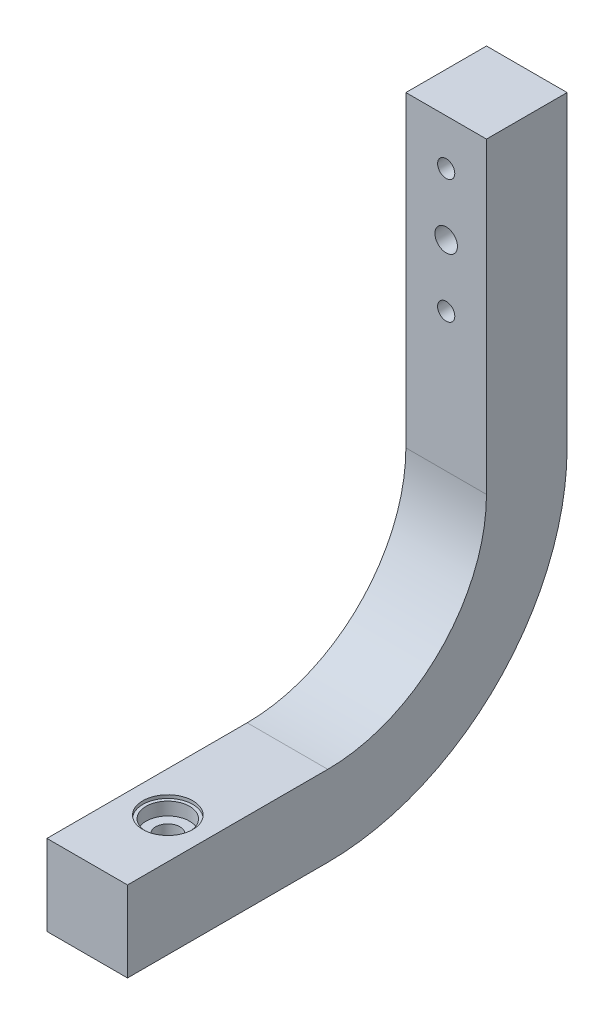
SolidWorks part; units mm, degrees
ref_plane "Front Plane" through (0, 0, 0) normal (0, 0, 1) x (1, 0, 0)
ref_plane "Top Plane" through (0, 0, 0) normal (0, 1, 0) x (1, 0, 0)
ref_plane "Right Plane" through (0, 0, 0) normal (1, 0, 0) x (0, 0, -1)
ref_axis "Z" through (0, 0, 86.1) along (0, 0, -1)
sketch "Sketch1" plane through (0, 0, 0) normal (1, 0, 0) x (0, 0, -1)
  line L0 (-15, 20) -> (0, 20)
  line L1 (0, 20) -> (0, -37.2682)
  line L2 (0, -32) -> (-49.8046, -81.8046) construction
  line L3 (-44.5364, -81.8046) -> (-66.8046, -81.8046)
  line L4 (-66.8046, -81.8046) -> (-66.8046, -66.8046) construction
  line L5 (-66.8046, -66.8046) -> (-44.5364, -66.8046)
  line L6 (-56.0178, -66.8046) -> (-15, -25.7868) construction
  line L7 (-15, -37.2682) -> (-15, 20)
  line L8 (-35.5089, -46.2957) -> (-24.9023, -56.9023) construction
  line L9 (-44.5364, -66.8046) -> (-56.0178, -66.8046) construction
  line L10 (-66.8046, -66.8046) -> (-81.8046, -66.8046)
  line L11 (-66.8046, -66.8046) -> (-66.8046, -81.8046) construction
  line L12 (-66.8046, -81.8046) -> (-81.8046, -81.8046)
  line L13 (-81.8046, -66.8046) -> (-81.8046, -81.8046)
  line L14 (-15, -25.7868) -> (-15, -37.2682) construction
  line L15 (0, -37.2682) -> (0, -32) construction
  line L16 (-49.8046, -81.8046) -> (-44.5364, -81.8046) construction
  arc A0 (-44.5364, -66.8046) -> (-15, -37.2682) centre (-44.5364, -37.2682) ccw
  arc A1 (-44.5364, -81.8046) -> (0, -37.2682) centre (-44.5364, -37.2682) ccw
  dimension "D1" = 15
  dimension "D2" = 66.8046
  dimension "D3" = 81.8046
  dimension "D4" = 20
  dimension "D5" = 135
  dimension "D6" = 49.8046
  dimension "D7" = 15
  dimension "D8" = 22.2682
extrude "Boss-Extrude1" add sketch "Sketch1" along normal blind 7.5 and the other way blind 7.5
sketch "Sketch3" plane through (0, -66.8046, 0) normal (0, 1, 0) x (1, 0, 0)
  line L0 (-8.25, 0) -> (8.25, 0) construction
  line L1 (0, -45.1) -> (0, 45.1) construction
  circle A0 centre (0, -66.8046) radius 2.25
  dimension "D2" = 4.5
  dimension "D1" = 66.8046
extrude "Cut-Extrude1" cut sketch "Sketch3" against normal through all
sketch "Sketch4" plane through (0, 0, 15) normal (0, 0, 1) x (1, 0, 0)
  line L0 (0, -11.5) -> (0, 11.5) construction
  circle A0 centre (0, 0) radius 2.1
  circle A1 centre (0, 11.5) radius 1.6
  circle A2 centre (0, -11.5) radius 1.6
  dimension "D1" = 4.2
  dimension "D3" = 3.2
  dimension "D2" = 23
extrude "Cut-Extrude2" cut sketch "Sketch4" against normal through all both and the other way through all
ref_axis "Axis1" through (0, -52.1687, 66.8046) along (0, 1, 0)
sketch "Sketch5" plane through (0, 0, 0) normal (1, 0, 0) x (0, 0, -1)
  line L0 (-62.7546, -78.8046) -> (-62.7546, -81.2046)
  line L1 (-62.7546, -81.2046) -> (-62.1546, -81.2046)
  line L2 (-62.1546, -81.2046) -> (-62.1546, -81.8046)
  line L3 (-62.1546, -81.8046) -> (-66.8046, -81.8046)
  line L4 (-66.8046, -81.8046) -> (-66.8046, -78.8046)
  line L5 (-66.8046, -78.8046) -> (-62.7546, -78.8046)
  line L6 (-66.8046, -74.3046) -> (-66.8046, -90.6731) construction
  line L7 (-66.8046, -74.3046) -> (-81.8046, -74.3046) construction
  line L8 (-66.8046, -69.8046) -> (-62.7546, -69.8046)
  line L9 (-66.8046, -66.8046) -> (-66.8046, -69.8046)
  line L10 (-62.1546, -66.8046) -> (-66.8046, -66.8046)
  line L11 (-62.1546, -67.4046) -> (-62.1546, -66.8046)
  line L12 (-62.7546, -67.4046) -> (-62.1546, -67.4046)
  line L13 (-62.7546, -69.8046) -> (-62.7546, -67.4046)
  line L16 (-66.8046, -52.1687) -> (-66.8046, -36.5447) construction
  line L17 (-81.8046, -66.8046) -> (-81.8046, -81.8046) construction
  line L18 (-66.8046, -66.8046) -> (-44.5364, -66.8046) construction
  dimension "D2" = 4.65
  dimension "D3" = 3
  dimension "D4" = 8.1
revolve "Cut-Revolve1" cut sketch "Sketch5" angle 360 about axis through (0, -52.1687, 66.8046) along (0, 1, 0)
equation "\"rbracket-width\"= \"L2Thickness\""
equation "\"D1@Boss-Extrude1\"=\"rbracket-width\"/2"
equation "\"D2@Boss-Extrude1\"=\"rbracket-width\"/2"
equation "\"EyeCaptureRadius\"= ( \"EyeDiameter\" + \"EyeClearance\" ) / 2"
equation "\"rbracket_planetocenterline_dist\"= \"BasePlaneDistance\""
equation "\"D2@Sketch1\"=\"rbracket_planetocenterline_dist\""
equation "\"EyeDiameter\" = 99.60916292"
equation "\"BasePlaneDistance\" = \"EyeDiameter\"/2+\"L2Thickness\"+\"EyeClearance\""
equation "\"EyeClearance\" = 2"
equation "\"D1@Sketch1\"=\"rbracket-width\""
equation "\"D3@Sketch1\"=(\"EyeDiameter\"+\"EyeClearance\"+\"EyeClearance\")/2 + \"L2Thickness\" + \"rbracket-width\""
equation "\"D6@Sketch1\"=\"EyeDiameter\"/2"
equation "\"D7@Sketch1\"=\"rbracket-width\""
equation "\"D1@Sketch3\"=\"BasePlaneDistance\""
equation "\"L2Thickness\" = 3.75 * \"shaft_diameter\""
equation "\"D8@Sketch1\"=\"rbracket_planetocenterline_dist\"/3"
equation "\"BearingFlangeOD\"= 7.5"
equation "\"BearingFlangeThickness\"= 0.75"
equation "\"BearingHousingID\"=4.5"
equation "\"BearingDepth\"= 6"
equation "\"PrinterFilamentThickness\"= 0.1"
equation "\"ApplyPrinterOffsets\"= 1"
equation "\"L2_ID\" = 20"
equation "\"vx\" = 50"
equation "\"vy\" = 10"
equation "\"vz\" = 100"
equation "\"parametric_end\" = 1"
equation "\"Rw_3_xx\" = -(\"vz\")/sqr((\"vx\")^2 + (\"vz\")^2)"
equation "\"Rw_3_xy\" = 0"
equation "\"Rw_3_xz\" = (\"vx\")/sqr((\"vx\")^2 + (\"vz\")^2)"
equation "\"Rw_3_zx\" = (\"vx\")/sqr((\"vx\")^2 + (\"vy\")^2 + (\"vz\")^2)"
equation "\"Rw_3_zy\" = (\"vy\")/sqr((\"vx\")^2 + (\"vy\")^2 + (\"vz\")^2)"
equation "\"Rw_3_zz\" = (\"vz\")/sqr((\"vx\")^2 + (\"vy\")^2 + (\"vz\")^2)"
equation "\"Rw_3_yx\" = (\"vx\")*(\"vy\")/sqr((\"vx\")^4 + (\"vx\")^2*(\"vy\")^2 + 2*(\"vx\")^2*(\"vz\")^2 + (\"vy\")^2*(\"vz\")^2 + (\"vz\")^4)"
equation "\"Rw_3_yy\" = -sqr((\"vx\")^2 + (\"vz\")^2)/sqr((\"vx\")^2 + (\"vy\")^2 + (\"vz\")^2)"
equation "\"Rw_3_yz\" = (\"vy\")*(\"vz\")/sqr((\"vx\")^4 + (\"vx\")^2*(\"vy\")^2 + 2*(\"vx\")^2*(\"vz\")^2 + (\"vy\")^2*(\"vz\")^2 + (\"vz\")^4)"
equation "\"O2Targx\" = -\"BasePlaneDistance\"*(\"vx\")*(\"vy\")/sqr((\"vx\")^4 + (\"vx\")^2*(\"vy\")^2 + 2*(\"vx\")^2*(\"vz\")^2 + (\"vy\")^2*(\"vz\")^2 + (\"vz\")^4)"
equation "\"O2Targy\" = \"BasePlaneDistance\"*sqr((\"vx\")^2 + (\"vz\")^2)/sqr((\"vx\")^2 + (\"vy\")^2 + (\"vz\")^2)"
equation "\"O2Targz\" = -\"BasePlaneDistance\"*(\"vy\")*(\"vz\")/sqr((\"vx\")^4 + (\"vx\")^2*(\"vy\")^2 + 2*(\"vx\")^2*(\"vz\")^2 + (\"vy\")^2*(\"vz\")^2 + (\"vz\")^4)"
equation "\"O2Targx_0\" = -(\"BasePlaneDistance\")*sqr((\"vx\")^2 + (\"vz\")^2)/sqr((\"vx\")^2 + (\"vy\")^2 + (\"vz\")^2)"
equation "\"O2Targy_0\" = -(\"BasePlaneDistance\")*(\"vy\")*(\"vz\")/sqr((\"vx\")^4 + (\"vx\")^2*(\"vy\")^2 + 2*(\"vx\")^2*(\"vz\")^2 + (\"vy\")^2*(\"vz\")^2 + (\"vz\")^4)"
equation "\"O2Targz_0\" = (\"BasePlaneDistance\")*(\"vx\")*(\"vy\")/sqr((\"vx\")^4 + (\"vx\")^2*(\"vy\")^2 + 2*(\"vx\")^2*(\"vz\")^2 + (\"vy\")^2*(\"vz\")^2 + (\"vz\")^4) + (\"BasePlaneDistance\")"
equation "\"theta2_s1\" = arcsin(((\"BasePlaneDistance\") - (\"O2Targz_0\"))/(\"BasePlaneDistance\")) + pi"
equation "\"theta2_s2\" = -arcsin(((\"BasePlaneDistance\") - (\"O2Targz_0\"))/(\"BasePlaneDistance\"))"
equation "\"theta1_s1\" = arcsin((\"O2Targy_0\")/((\"BasePlaneDistance\")*cos((\"Theta2\")))) + pi"
equation "\"theta1_s2\" = -arcsin((\"O2Targy_0\")/((\"BasePlaneDistance\")*cos((\"Theta2\"))))"
equation "\"theta1_s3\" = -arccos(-(\"O2Targx_0\")/((\"BasePlaneDistance\")*cos((\"Theta2\")))) + 2*pi"
equation "\"theta1_s4\" = arccos(-(\"O2Targx_0\")/((\"BasePlaneDistance\")*cos((\"Theta2\"))))"
equation "\"Theta1\" = \"theta1_s2\" 'so far, theta1_s1 and theta1_s4 have agreed, and they agree with the sw constraint solver"
equation "\"Theta2\" = \"theta2_s2\""
equation "\"o2_x\" = -(\"BasePlaneDistance\")*cos((\"Theta1\"))*cos((\"Theta2\"))"
equation "\"o2_y\" = -(\"BasePlaneDistance\")*sin((\"Theta1\"))*cos((\"Theta2\"))"
equation "\"o2_z\" = (\"BasePlaneDistance\")*(sin((\"Theta2\")) + 1)"
equation "\"o1_x\" = (\"BasePlaneDistance\")*sin((\"Theta1\"))"
equation "\"o1_y\" = -(\"BasePlaneDistance\")*cos((\"Theta1\"))"
equation "\"o1_z\" = (\"BasePlaneDistance\")"
equation "\"Actuator1_Theta\" = atn(\"vx\"/\"vz\") 'ik solution for the single link joint"
equation "\"Actuator2_Theta\" = \"Theta1\"  'ik solution for the double link joint"
equation "\"MotorBaseThickness\" = 3 "
equation "\"BaseThickness\" = 3 "
equation "\"EncoderToMagnetAirgap\" = 1 'Encoder to magnet airgap"
equation "\"EncoderHeight\" = 1.192  'Height of the encoder"
equation "\"MagnetThickness\" = 0.5  'Magnet thickness"
equation "\"pcb_thickness\" = 1.6  'Thickness of the PCB"
equation "\"pcb_outer_diameter\" = 32 'the OD of the pcb"
equation "\"shaft_diameter\" = 4"
equation "\"D2@Sketch3\"=\"shaft_diameter\"*1.125"
equation "\"D2@Sketch5\"=\"ApplyPrinterOffsets\"*\"PrinterFilamentThickness\"/2+4.6"
equation "\"D4@Sketch5\"=\"ApplyPrinterOffsets\"*\"PrinterFilamentThickness\"+8"
